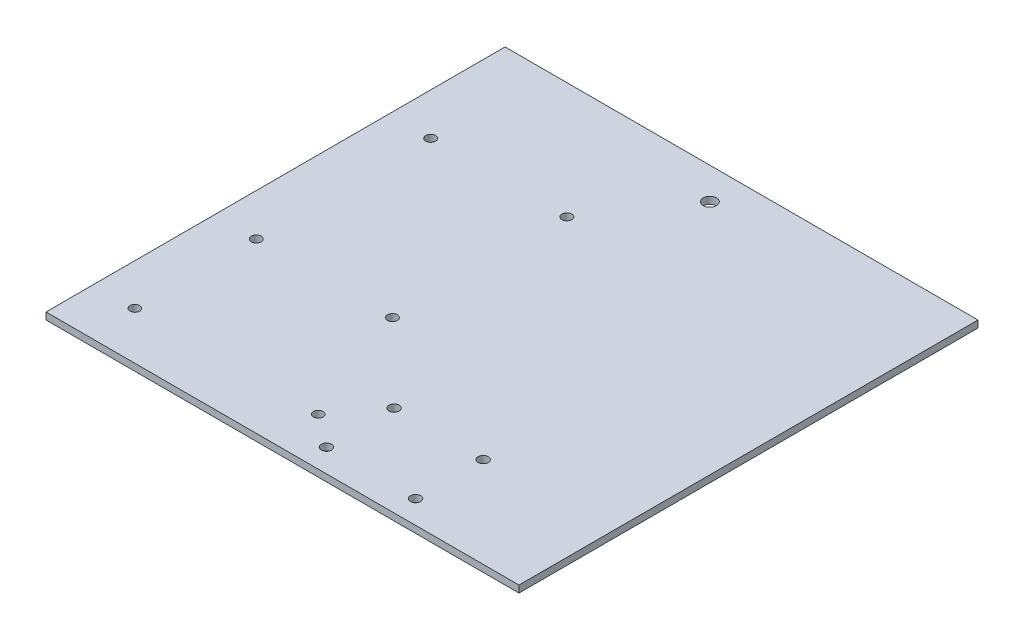
SolidWorks part; units mm, degrees
ref_plane "Front Plane" through (0, 0, 0) normal (0, 0, 1) x (1, 0, 0)
ref_plane "Top Plane" through (0, 0, 0) normal (0, 1, 0) x (1, 0, 0)
ref_plane "Right Plane" through (0, 0, 0) normal (1, 0, 0) x (0, 0, -1)
sketch "Sketch1" plane through (0, 0, 0) normal (0, 1, 0) x (1, 0, 0)
  line L1 (-94.869, -92.075) -> (94.869, -92.075)
  line L2 (-94.869, -92.075) -> (-94.869, 92.075)
  line L3 (-94.869, 92.075) -> (94.869, 92.075)
  line L4 (94.869, -92.075) -> (94.869, 92.075)
  line L5 (-94.869, -92.075) -> (94.869, 92.075) construction
  line L6 (-94.869, 92.075) -> (94.869, -92.075) construction
  point P0 (0, 0)
  dimension "D1" = 189.738
  dimension "D2" = 184.15
extrude "Boss-Extrude1" add sketch "Sketch1" along normal blind 2.794
sketch "Sketch2" plane through (0, 2.794, 0) normal (0, 1, 0) x (1, 0, 0)
  line L2 (94.869, 92.075) -> (-94.869, 92.075) construction
  circle A0 centre (0, 79.375) radius 2.6797
  point P4 (0, 92.075)
  dimension "D1" = 5.3594
  dimension "D2" = 12.7
extrude "Cut-Extrude1" cut sketch "Sketch2" against normal through all
sketch "Sketch4" plane through (0, 2.794, 0) normal (0, 1, 0) x (1, 0, 0)
  line L7 (5.481, -52.725) -> (46.661, -52.725) construction
  line L8 (5.481, -52.725) -> (5.481, -85.725) construction
  line L9 (5.481, -85.725) -> (46.661, -85.725) construction
  line L10 (46.661, -52.725) -> (46.661, -85.725) construction
  line L11 (5.481, -52.725) -> (46.661, -85.725) construction
  line L12 (5.481, -85.725) -> (46.661, -52.725) construction
  line L13 (-82.169, -47.405) -> (-0.869, -47.405) construction
  line L14 (-82.169, -47.405) -> (-82.169, -98.425) construction
  line L15 (-82.169, -98.425) -> (-0.869, -98.425) construction
  line L16 (-0.869, -47.405) -> (-0.869, -98.425) construction
  line L17 (-82.169, -47.405) -> (-0.869, -98.425) construction
  line L18 (-82.169, -98.425) -> (-0.869, -47.405) construction
  line L19 (5.481, -69.225) -> (46.661, -69.225) construction
  line L24 (-94.869, 92.075) -> (-94.869, -92.075) construction
  line L25 (-94.869, -92.075) -> (94.869, -92.075) construction
  line L34 (-82.169, 53.685) -> (-19.299, 53.685) construction
  line L41 (-82.169, 53.685) -> (-82.169, -41.055) construction
  line L42 (-82.169, -41.055) -> (-19.299, -41.055) construction
  line L43 (-19.299, 53.685) -> (-19.299, -41.055) construction
  circle A2 centre (-78.2965, -72.9925) radius 1.9362
  circle A3 centre (-4.7415, -72.9925) radius 1.9362
  circle A4 centre (8.356, -55.65) radius 2.0487
  circle A5 centre (44.106, -55.65) radius 2.0487
  circle A6 centre (44.106, -82.8) radius 2.0487
  circle A7 centre (8.356, -82.8) radius 2.0487
  circle A16 centre (-78.039, 45.43) radius 1.98
  circle A21 centre (-23.429, 45.43) radius 1.98
  circle A22 centre (-23.429, -24.545) radius 1.98
  circle A23 centre (-78.039, -24.545) radius 1.98
  point P11 (26.071, -69.225)
  point P16 (-41.519, -72.915)
  dimension "D13" = 3.8724
  dimension "D15" = 3.8724
  dimension "D20" = 4.0974
  dimension "D24" = 6.35
  dimension "D30" = 2
  dimension "D31" = 2
  dimension "D32" = 16.51
  dimension "D29" = 3.96
  dimension "D35" = 4.13
  dimension "D36" = 4.13
  dimension "D38" = 16.51
  dimension "D39" = 4.13
  dimension "D40" = 6.35
  dimension "D8" = 41.18
  dimension "D9" = 33
  dimension "D10" = 81.3
  dimension "D11" = 51.02
  dimension "D12" = 12.7
  dimension "D14" = 25.4325
  dimension "D16" = 25.4325
  dimension "D17" = 3.8725
  dimension "D18" = 3.8725
  dimension "D19" = 35.75
  dimension "D21" = 2.925
  dimension "D22" = 2.555
  dimension "D23" = 16.5
  dimension "D25" = 6.35
  dimension "D26" = 6.35
  dimension "D27" = 94.74
  dimension "D28" = 62.87
  dimension "D41" = 12.7
extrude "Cut-Extrude3" cut sketch "Sketch4" against normal through all contours A3 | A2 | A5 | A4 | A7 | A6 | A22 | A23 | A16 | A21
